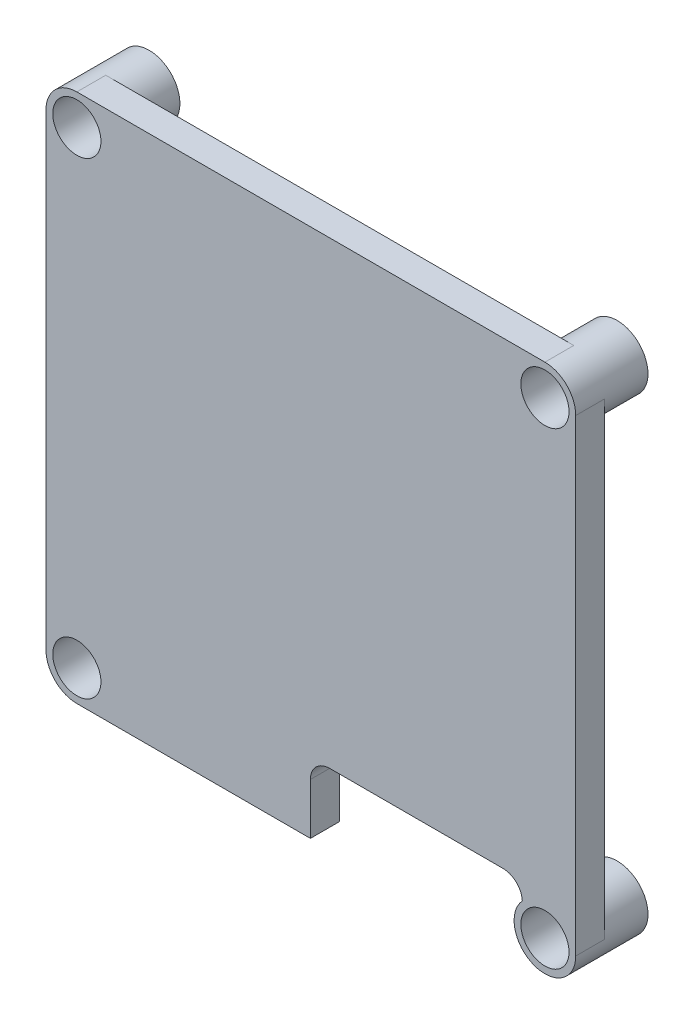
SolidWorks part; units mm, degrees
ref_plane "Front Plane" through (0, 0, 0) normal (0, 0, 1) x (1, 0, 0)
ref_plane "Top Plane" through (0, 0, 0) normal (0, 1, 0) x (1, 0, 0)
ref_plane "Right Plane" through (0, 0, 0) normal (1, 0, 0) x (0, 0, -1)
sketch "Sketch1" plane through (0, 0, 0) normal (0, 0, 1) x (1, 0, 0)
  circle A0 centre (-12.15, -12.15) radius 1 construction
  circle A1 centre (12.15, -12.15) radius 1 construction
  circle A2 centre (12.15, 12.15) radius 1 construction
  circle A3 centre (-12.15, 12.15) radius 1 construction
  circle A4 centre (-12.15, -12.15) radius 1
  circle A5 centre (12.15, -12.15) radius 1
  circle A6 centre (12.15, 12.15) radius 1
  circle A7 centre (-12.15, 12.15) radius 1
  circle A8 centre (-12.15, 12.15) radius 1.6
  circle A9 centre (12.15, 12.15) radius 1.6
  circle A10 centre (12.15, -12.15) radius 1.6
  circle A11 centre (-12.15, -12.15) radius 1.6
  circle A12 centre (-12.15, 12.15) radius 1.25
  circle A13 centre (12.15, 12.15) radius 1.25
  circle A14 centre (12.15, -12.15) radius 1.25
  circle A15 centre (-12.15, -12.15) radius 1.25
  dimension "D2" = 2.5
  dimension "D1" = 3.2
extrude "Boss-Extrude1" add sketch "Sketch1" along normal blind 2.25 contours A8 A12 | A9 A13 | A10 A14 | A11 A15
sketch "Sketch2" plane through (0, 0, 2.25) normal (0, 0, 1) x (1, 0, 0)
  line L0 (-12.15, 13.75) -> (12.15, 13.75)
  line L1 (13.75, 12.15) -> (13.75, -12.15)
  line L2 (-13.75, 12.15) -> (-13.75, -12.15)
  line L3 (-12.15, -13.75) -> (-0.025, -13.75)
  line L4 (-0.025, -13.75) -> (-0.025, -10.1)
  line L5 (-0.025, -10.1) -> (10.975, -10.1)
  line L6 (10.975, -10.1) -> (10.975, -11.064)
  line L7 (0.475, -10.6) -> (0.475, -13.9) construction
  line L8 (4.125, -10.6) -> (0.875, -10.6) construction
  line L9 (10.475, -13.9) -> (10.475, -10.6) construction
  circle A4 centre (12.15, 12.15) radius 1.6
  circle A5 centre (12.15, -12.15) radius 1.6
  circle A6 centre (-12.15, -12.15) radius 1.6
  circle A7 centre (-12.15, 12.15) radius 1.6
  circle A12 centre (-12.15, -12.15) radius 1.25
  circle A13 centre (12.15, -12.15) radius 1.25
  circle A14 centre (12.15, 12.15) radius 1.25
  circle A15 centre (-12.15, 12.15) radius 1.25
  circle A16 centre (-12.15, 12.15) radius 1.25 construction
  circle A17 centre (-12.15, 12.15) radius 1.6 construction
  circle A18 centre (12.15, 12.15) radius 1.25 construction
  circle A19 centre (12.15, -12.15) radius 1.25 construction
  circle A20 centre (12.15, -12.15) radius 1.6 construction
  circle A21 centre (12.15, 12.15) radius 1.6 construction
  circle A22 centre (-12.15, -12.15) radius 1.25 construction
  circle A23 centre (-12.15, -12.15) radius 1.6 construction
  point P1 (0, 0)
  point P3 (0, 0)
  point P7 (0, 0)
  point P29 (10.975, -10.582)
  point P39 (0, 0)
  point P43 (0, 0)
  point P47 (13.75, -12.15)
  point P48 (13.75, -12.15)
  point P53 (0, 0)
  point P54 (0, 0)
  dimension "D1" = 0.5
  dimension "D2" = 0.5
  dimension "D3" = 0.5
extrude "Boss-Extrude2" add sketch "Sketch2" along normal blind 1.5
fillet "Fillet1" radius 1 2 edges at (10.975, -10.1, 3) (-0.025, -10.1, 3)
